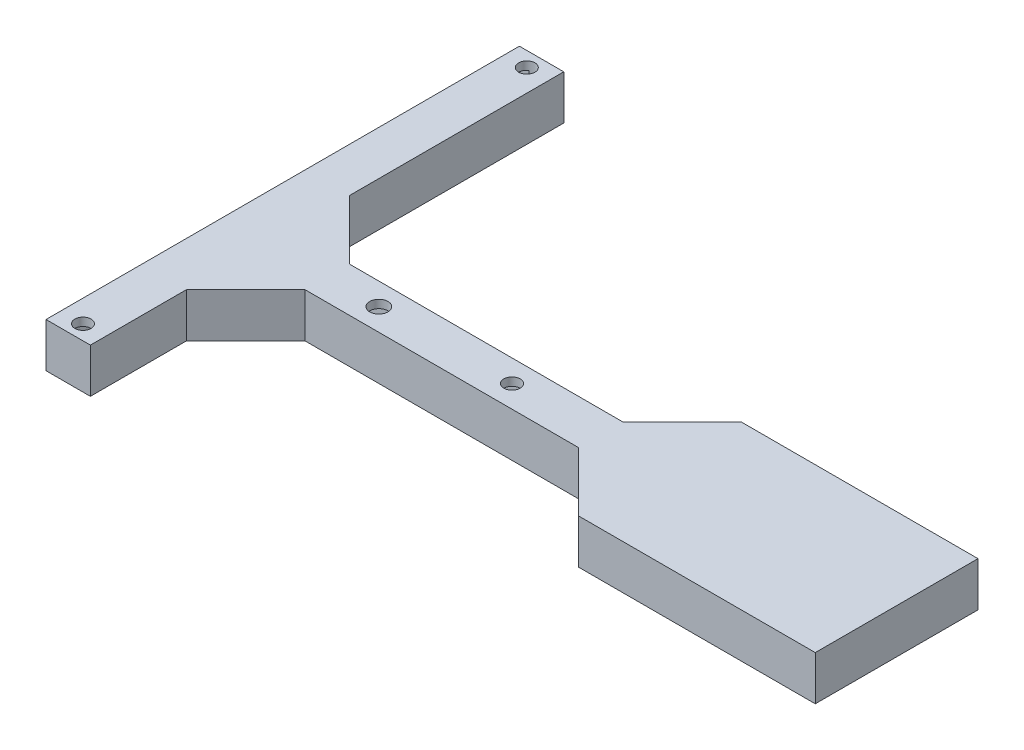
SolidWorks part; units mm, degrees
other "Markup1"
sketch "Sketch3" plane through (-227.5, 0, 60) normal (-0.1992, -0.7239, 0.6606) x (-0.1327, -0.6479, -0.75)
ref_plane "Front Plane" through (0, 0, 0) normal (0, 0, 1) x (1, 0, 0)
ref_plane "Top Plane" through (0, 0, 0) normal (0, 1, 0) x (1, 0, 0)
ref_plane "Right Plane" through (0, 0, 0) normal (1, 0, 0) x (0, 0, -1)
sketch "Sketch1" plane through (0, 0, 0) normal (0, 1, 0) x (1, 0, 0)
  line L0 (0, 0) -> (-220, 0) construction
  line L1 (-220, 0) -> (-220, -60) construction
  line L2 (-220, -60) -> (-220, 0) construction
  line L3 (-220, 0) -> (-220, 100) construction
  line L4 (-227.5, 100) -> (-212.5, 100)
  line L5 (-212.5, 100) -> (-212.5, 7.5)
  line L6 (0, -7.5) -> (0, 7.5)
  line L7 (-80, 7.5) -> (-212.5, 7.5)
  line L8 (-80, -7.5) -> (-212.5, -7.5)
  line L9 (-212.5, -7.5) -> (-212.5, -60)
  line L10 (-212.5, -60) -> (-227.5, -60)
  line L11 (-227.5, -60) -> (-227.5, 100)
  line L12 (-80, 7.5) -> (-80, 27.5)
  line L13 (-80, 27.5) -> (0, 27.5)
  line L14 (0, 27.5) -> (0, 7.5)
  line L15 (0, -7.5) -> (0, -27.5)
  line L16 (0, -27.5) -> (-80, -27.5)
  line L17 (-80, -27.5) -> (-80, -7.5)
  point P8 (-220, 100)
  point P12 (0, 0)
  dimension "D1" = 15
  dimension "D2" = 100
  dimension "D3" = 60
  dimension "D4" = 220
  dimension "D5" = 20
  dimension "D6" = 80
extrude "Boss-Extrude1" add sketch "Sketch1" along normal blind 15
shell "Shell1" thickness 2.75 removed face at (-135.4167, 0, -6.6667)
sketch "Sketch2" plane through (0, 15, 0) normal (0, 1, 0) x (1, 0, 0)
  line L0 (-220, 100) -> (-220, -60) construction
  line L1 (-212.5, 100) -> (-227.5, 100) construction
  line L2 (-227.5, -60) -> (-212.5, -60) construction
  line L3 (-220, -60) -> (-220, 0) construction
  line L4 (-220, 0) -> (0, 0) construction
  circle A0 centre (-130, 0) radius 2.75
  circle A1 centre (-220, 95) radius 2.75
  circle A2 centre (-220, -55) radius 2.75
  circle A3 centre (-175, 0) radius 3.0718
  dimension "D2" = 5.5
  dimension "D1" = 5
  dimension "D3" = 5
  dimension "D4" = 45
  dimension "D5" = 45
extrude "Cut-Extrude1" cut sketch "Sketch2" against normal blind 10
chamfer "Chamfer1" distance 20 angle 45 4 edges at (-212.5, 7.5, -7.5) (-212.5, 7.5, 7.5) (-80, 7.5, -7.5) (-80, 7.5, 7.5)
